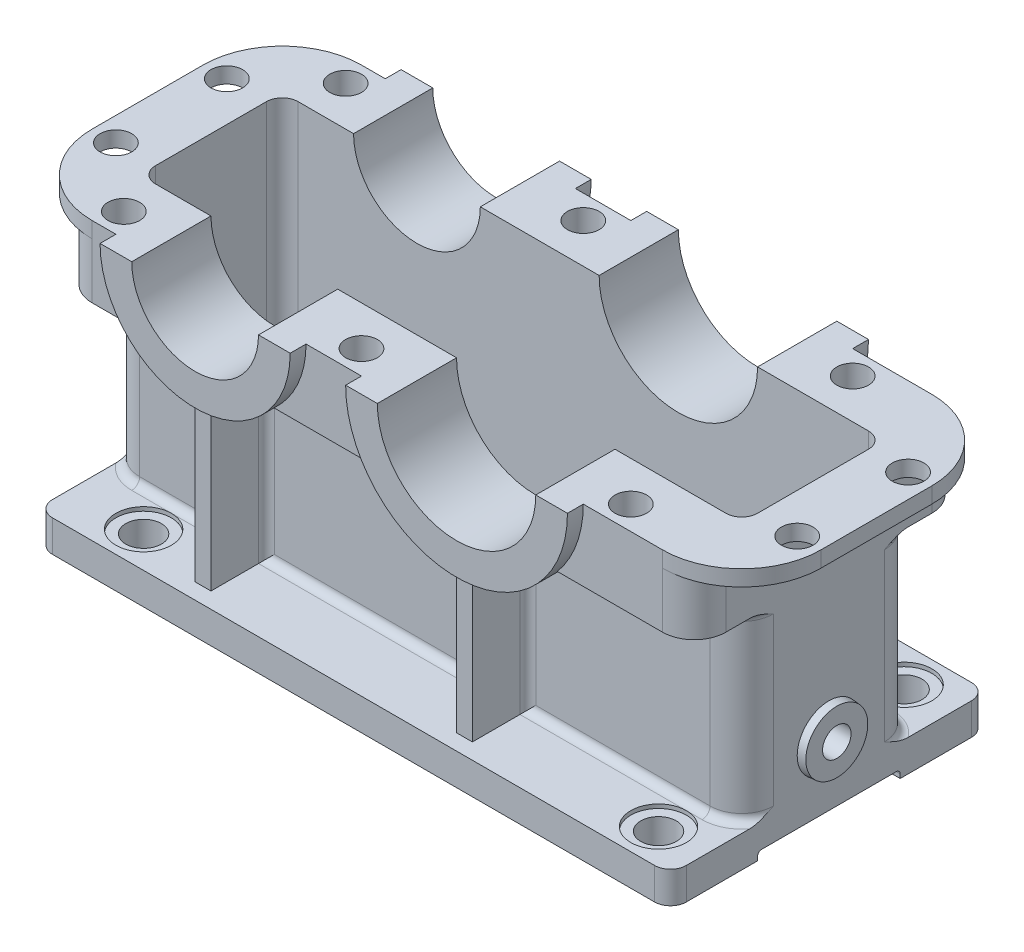
SolidWorks part; units mm, degrees
ref_plane "前视" through (0, 0, 0) normal (0, 0, 1) x (1, 0, 0)
ref_plane "上视" through (0, 0, 0) normal (0, 1, 0) x (1, 0, 0)
ref_plane "右视" through (0, 0, 0) normal (1, 0, 0) x (0, 0, -1)
sketch "草图1" plane through (0, 0, 0) normal (0, 1, 0) x (1, 0, 0)
  line L1 (-480, 110) -> (240, 110)
  line L2 (-520, 70) -> (-520, -70)
  line L3 (-480, -110) -> (240, -110)
  line L4 (280, 70) -> (280, -70)
  arc A0 (-520, 70) -> (-480, 110) centre (-480, 70) cw
  arc A1 (280, 70) -> (240, 110) centre (240, 70) ccw
  arc A2 (240, -110) -> (280, -70) centre (240, -70) ccw
  arc A3 (-520, -70) -> (-480, -110) centre (-480, -70) ccw
  point P9 (-520, -110)
  point P12 (280, -110)
  point P15 (280, 110)
  dimension "D5" = 40
  dimension "D1" = 800
  dimension "D2" = 220
  dimension "D3" = 110
  dimension "D4" = 280
extrude "拉伸1" add sketch "草图1" along normal blind 300
sketch "草图2" plane through (0, 300, 0) normal (0, 1, 0) x (1, 0, 0)
  line L1 (-480, 170) -> (240, 170)
  line L2 (-580, 70) -> (-580, -70)
  line L3 (-480, -170) -> (240, -170)
  line L4 (340, 70) -> (340, -70)
  arc A0 (-480, 170) -> (-580, 70) centre (-480, 70) ccw
  arc A1 (-580, -70) -> (-480, -170) centre (-480, -70) ccw
  arc A2 (240, -170) -> (340, -70) centre (240, -70) ccw
  arc A3 (240, 170) -> (340, 70) centre (240, 70) cw
  point P9 (-580, -170)
  point P12 (340, -170)
  point P15 (340, 170)
  dimension "D5" = 100
  dimension "D1" = 920
  dimension "D2" = 340
  dimension "D3" = 340
  dimension "D4" = 170
extrude "拉伸2" add sketch "草图2" along normal blind 20
shell "抽壳1" thickness 20 removed face at (-120, 320, 0)
sketch "草图3" plane through (0, 0, 0) normal (0, -1, 0) x (-1, 0, 0)
  line L1 (-280, -70) -> (-280, 70) construction
  line L2 (-260, 200) -> (500, 200)
  line L3 (-280, 180) -> (-280, -180)
  line L4 (-260, -200) -> (500, -200)
  line L5 (520, 180) -> (520, -180)
  line L7 (520, 70) -> (520, -70) construction
  arc A0 (-260, 200) -> (-280, 180) centre (-260, 180) ccw
  arc A1 (520, 180) -> (500, 200) centre (500, 180) ccw
  arc A2 (500, -200) -> (520, -180) centre (500, -180) ccw
  arc A3 (-280, -180) -> (-260, -200) centre (-260, -180) ccw
  point P10 (-280, 200)
  point P17 (-280, -200)
  dimension "D3" = 20
  dimension "D1" = 400
  dimension "D2" = 200
extrude "拉伸3" add sketch "草图3" along normal blind 40
sketch "草图5" plane through (0, 0, 90) normal (0, 0, 1) x (1, 0, 0)
  line L0 (-480, 320) -> (240, 320) construction
  line L2 (-450, 320) -> (-210, 320)
  line L3 (-140, 320) -> (140, 320)
  arc A0 (-450, 320) -> (-210, 320) centre (-330, 320) ccw
  arc A1 (-140, 320) -> (140, 320) centre (0, 320) ccw
  dimension "D2" = 280
  dimension "D3" = 240
  dimension "D1" = 330
sketch "草图6" plane through (0, 320, 0) normal (0, 1, 0) x (1, 0, 0)
  line L0 (-480, -170) -> (240, -170) construction
  line L1 (280, -70) -> (280, -180) construction
  line L2 (-480, -110) -> (240, -110) construction
  line L3 (-520, -180) -> (-520, -70) construction
  line L4 (-480, -170) -> (240, -170)
  line L5 (280, -70) -> (280, -130)
  line L6 (-480, -110) -> (240, -110)
  line L7 (-520, -130) -> (-520, -70)
  arc A0 (240, -110) -> (280, -70) centre (240, -70) ccw construction
  arc A1 (-520, -70) -> (-480, -110) centre (-480, -70) ccw construction
  arc A2 (240, -110) -> (280, -70) centre (240, -70) ccw
  arc A3 (-520, -70) -> (-480, -110) centre (-480, -70) ccw
  arc A4 (-480, -170) -> (-520, -130) centre (-480, -130) cw
  arc A5 (280, -130) -> (240, -170) centre (240, -130) cw
  dimension "D1" = 40
extrude "拉伸7" add sketch "草图5" along normal blind 100
extrude "拉伸5" add sketch "草图6" against normal blind 90
sketch "草图12" plane through (0, 0, 0) normal (-1, 0, 0) x (0, 0, 1)
  line L0 (180, 186.824) -> (180, -20)
  line L1 (110, 230) -> (110, 0) construction
  dimension "D1" = 70
rib "筋1" sketch "草图12" sketch "草图12" thickness 20 extrusion direction parallel to sketch draft on no parameters "D1"=20
ref_plane "基准面1" through (-330, 0, 0) normal (1, 0, 0) x (0, 0, -1)
sketch "草图23" plane through (-330, 0, 0) normal (1, 0, 0) x (0, 0, -1)
  line L0 (-180, 221.8512) -> (-180, -18.5118)
  line L1 (-110, 0) -> (-110, 180.3576) construction
  dimension "D1" = 70
rib "筋2" sketch "草图23" sketch "草图23" thickness 20 extrusion direction parallel to sketch draft on no parameters "D1"=20
sketch "草图4" plane through (280, 0, 0) normal (1, 0, 0) x (0, 0, -1)
  line L2 (180, -40) -> (-180, -40) construction
  line L3 (-85, -30) -> (85, -30)
  line L4 (-90, -35) -> (-90, -40)
  line L5 (-90, -40) -> (90, -40)
  line L6 (90, -35) -> (90, -40)
  arc A0 (90, -35) -> (85, -30) centre (85, -35) ccw
  arc A1 (-90, -35) -> (-85, -30) centre (-85, -35) cw
  point P8 (90, -30)
  dimension "D4" = 5
  dimension "D1" = 180
  dimension "D2" = 90
  dimension "D3" = 10
extrude "切除-拉伸1" cut sketch "草图4" against normal through all
sketch "草图18" plane through (0, 0, 190) normal (0, 0, 1) x (1, 0, 0)
  line L0 (-210, 320) -> (-450, 320) construction
  line L1 (140, 320) -> (-140, 320) construction
  circle A0 centre (-330, 320) radius 80
  circle A1 centre (0, 320) radius 100
  dimension "D1" = 200
  dimension "D2" = 160
extrude "切除-拉伸2" cut sketch "草图18" against normal up to next
sketch "草图8" plane through (0, 320, 0) normal (0, 1, 0) x (1, 0, 0)
  circle A0 centre (310, -70) radius 20
  circle A1 centre (-550, -70) radius 20
  circle A3 centre (-470, -140) radius 20
  circle A4 centre (-170, -140) radius 20
  circle A5 centre (170, -140) radius 20
  dimension "D2" = 70
  dimension "D3" = 70
  dimension "D4" = 40
  dimension "D5" = 40
  dimension "D7" = 860
  dimension "D10" = 140
  dimension "D11" = 170
  dimension "D12" = 40
  dimension "D13" = 40
  dimension "D14" = 40
  dimension "D15" = 140
  dimension "D16" = 140
  dimension "D17" = 300
  dimension "D18" = 340
  dimension "D6" = 550
extrude "切除-拉伸4" cut sketch "草图8" against normal up to next
hole_wizard "孔1" positions "3D草图1" profile "草图22" legacy
sketch3d "3D草图1"
  line L0 (260, 0, 200) -> (-500, 0, 200) construction
  line L1 (280, 0, 70) -> (280, 0, 180) construction
  point P0 (220, 0, 155)
  dimension "D1" = 45
  dimension "D2" = 60
sketch "草图22" plane through (220, 0, 155) normal (1, 0, 0) x (0, 0, 1)
  line L0 (0, 0) -> (0, 40)
  line L1 (0, 40) -> (22.5, 40)
  line L2 (22.5, 40) -> (22.5, 5)
  line L3 (22.5, 5) -> (35, 5)
  line L4 (35, 0) -> (0, 0)
  line L5 (0, -11.3109) -> (0, 121.1557) construction
  line L6 (0, 40) -> (-22.5, 40) construction
  line L7 (35, 5) -> (35, 0)
  dimension "眻噤" = 45
  dimension "旮僅" = 40
  dimension "翐諧眻噤" = 70
  dimension "翐諧旮僅" = 5
  dimension "絳芛褒僅" = 180
pattern_linear "阵列(线性)1" count 2 spacing 650 along (-1, 0, 0) of "孔1"
mirror "镜向1" about plane through (0, 0, 0) normal (0, 0, 1) of "筋2", "筋1", "切除-拉伸4", "切除-拉伸2", "拉伸5", "拉伸7", "阵列(线性)1"
sketch "草图14" plane through (280, 0, 0) normal (-1, 0, 0) x (0, 0, 1)
  line L0 (-112.7635, 0) -> (168.8873, 0) construction
  line L3 (-85, -30) -> (85, -30) construction
  circle A0 centre (0, 50) radius 40
  dimension "D1" = 80
  dimension "D2" = 80
extrude "拉伸6" add sketch "草图14" against normal blind 10 draft 5
sketch "草图15" plane through (290, 0, 0) normal (1, 0, 0) x (0, 0, -1)
  circle A0 centre (0, 50) radius 18
  dimension "D1" = 36
extrude "切除-拉伸6" cut sketch "草图15" against normal up to next
fillet "圆角1" radius 10 18 edges at (268.2843, 230, 98.2843) (-508.2843, 230, 98.2843) (-377.0706, 209.6172, 110) (-282.9294, 209.6172, 110) (-178.9328, 230, 110) (63.6575, 195.3095, 110) (-63.6575, 195.3095, 110) (173.619, 230, 110) (-444.6863, 230, 110) (125, 0, 110) (10, 90.1788, 110) (-10, 90.1788, 110) (-165, 0, 110) (-320, 100.2087, 110) (-410, 0, 110) (-340, 100.2087, 110)
fillet "圆角2" radius 10 18 edges at (-508.2843, 230, -98.2843) (-377.0706, 209.6172, -110) (-444.6863, 230, -110) (-410, 0, -110) (-340, 100.2087, -110) (-10, 90.1788, -110) (-63.6575, 195.3095, -110) (-178.9328, 230, -110) (-282.9294, 209.6172, -110) (-320, 100.2087, -110) (-165, 0, -110) (125, 0, -110) (173.619, 230, -110) (63.6575, 195.3095, -110) (10, 90.1788, -110) (268.2843, 230, -98.2843)
sketch "草图24" plane through (-520, 0, 0) normal (-1, 0, 0) x (0, 0, 1)
  line L0 (-85, -30) -> (85, -30) construction
  circle A0 centre (0, 50) radius 40
  dimension "D1" = 80
  dimension "D2" = 80
extrude "凸台-拉伸1" add sketch "草图24" along normal blind 10
sketch "草图25" plane through (-530, 0, 0) normal (-1, 0, 0) x (0, 0, 1)
  circle A0 centre (0, 50) radius 18
  dimension "D1" = 36
extrude "切除-拉伸7" cut sketch "草图25" against normal up to next
